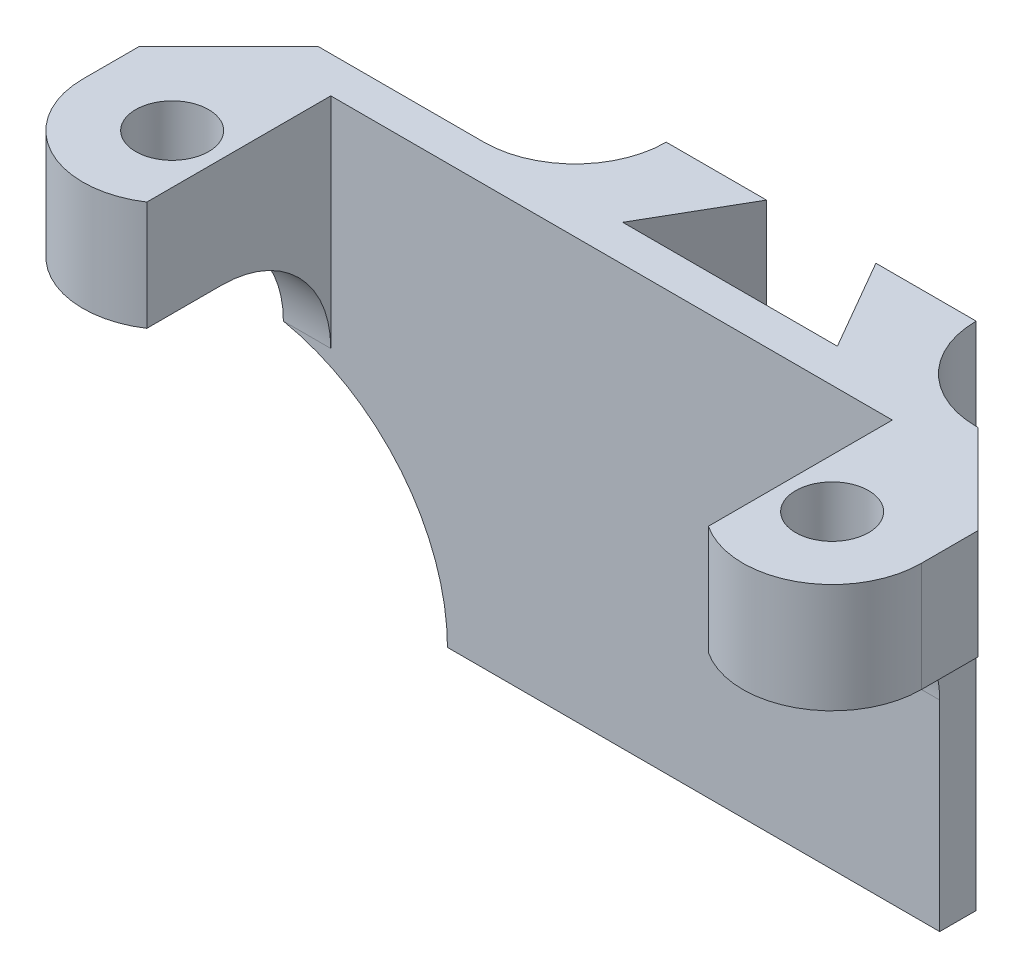
SolidWorks part; units mm, degrees
material "ABS"
ref_plane "Front Plane" through (0, 0, 0) normal (0, 0, 1) x (1, 0, 0)
ref_plane "Top Plane" through (0, 0, 0) normal (0, 1, 0) x (1, 0, 0)
ref_plane "Right Plane" through (0, 0, 0) normal (1, 0, 0) x (0, 0, -1)
sketch "Sketch1" plane through (0, 0, 0) normal (0, 0, 1) x (1, 0, 0)
  line L0 (-15, 15) -> (15, 15)
  line L1 (15, 15) -> (15, -15)
  line L2 (15, -15) -> (-15, -15)
  line L3 (-15, -15) -> (-15, 15)
  line L4 (-15, 0) -> (15, 0) construction
  line L5 (-15, 5) -> (-23, 5)
  line L6 (-23, 5) -> (-23, -1)
  line L7 (-23, -1) -> (-18, -1)
  line L8 (-18, -1) -> (-18, -18)
  line L9 (-18, -18) -> (18, -18)
  line L10 (18, -18) -> (18, -1)
  line L11 (18, -1) -> (23, -1)
  line L12 (23, -1) -> (23, 5)
  line L13 (23, 5) -> (15, 5)
  line L14 (-15, 5) -> (15, 5)
  point P6 (0, 0)
  dimension "D1" = 30
  dimension "D2" = 30
  dimension "D3" = 20
  dimension "D4" = 3
  dimension "D5" = 3
  dimension "D6" = 5
  dimension "D7" = 6
extrude "Extrude1" add sketch "Sketch1" along normal mid plane 16 contours L12 L13 L1 L2 L3 L5 L6 L7 L8 L9 L10 L11 | L4 L3 L2 L1 | L3 L4 L1 L14
sketch "Sketch2" plane through (0, 0, 0) normal (0, 1, 0) x (1, 0, 0)
  line L0 (-15.4, 0) -> (15.4, 0) construction
  line L1 (0, -6) -> (0, 6) construction
  line L2 (-15.4, -6) -> (-15.4, 6)
  line L3 (-15.4, 6) -> (15.4, 6)
  line L4 (15.4, 6) -> (15.4, -6)
  line L5 (15.4, -6) -> (-15.4, -6)
  line L6 (-18.1, 0) -> (-15.4, 0) construction
  line L7 (15.4, 0) -> (18.1, 0) construction
  line L8 (23, -3.1) -> (18.1, -8)
  line L9 (23, -8) -> (23, 8) construction
  line L11 (23, -8) -> (-23, -8) construction
  line L12 (18.1, -8) -> (23, -8)
  line L14 (23, -8) -> (23, -3.1)
  line L15 (18.1, 8) -> (23, 3.1)
  line L17 (23, 8) -> (-23, 8) construction
  line L18 (23, 3.1) -> (23, 8)
  line L20 (23, 8) -> (18.1, 8)
  line L21 (-18.1, 8) -> (-23, 3.1)
  line L22 (-23, -8) -> (-23, 8) construction
  line L23 (-23, 3.1) -> (-23, 8)
  line L24 (-23, 8) -> (-18.1, 8)
  line L25 (-23, -3.1) -> (-18.1, -8)
  line L26 (-18.1, -8) -> (-23, -8)
  line L27 (-23, -8) -> (-23, -3.1)
  line L28 (-11.4, 4) -> (11.4, 4)
  line L29 (-11.4, 4) -> (-11.4, -4)
  line L30 (-11.4, -4) -> (11.4, -4)
  line L31 (11.4, -4) -> (11.4, 4)
  circle A0 centre (-18.1, 0) radius 2
  circle A1 centre (18.1, 0) radius 2
  point P2 (0, 0)
  point P6 (0, 0)
  point P46 (-11.4, 0)
  point P47 (11.4, 0)
  dimension "D4" = 4
  dimension "D1" = 12
  dimension "D2" = 30.8
  dimension "D3" = 36.2
  dimension "D5" = 2
  dimension "D6" = 4
  dimension "D7" = 4
extrude "Extrude2" cut sketch "Sketch2" against normal blind 20 from surface at 5 contours L27 L26 L25 | A0 | L24 L23 L21 | L30 L31 L28 L29 | L5 L4 L3 L2 L31 L30 L29 L28 | L18 L20 L15 | A1 | L12 L14 L8 starting at face at (0, 5, 0)
sketch "Sketch5" plane through (0, 0, 0) normal (0, 0, 1) x (1, 0, 0)
  line L0 (-18, -1) -> (-18, -18)
  line L1 (18, -1) -> (18, -18)
  line L2 (18, -18) -> (-18, -18)
  line L3 (-18, -1) -> (18, -1)
extrude "Extrude10" cut sketch "Sketch5" along normal up to surface (14 mm away) from vertex
sketch "Sketch4" plane through (0, 0, 0) normal (0, 1, 0) x (1, 0, 0)
  line L0 (13, 8) -> (13, 13)
  line L1 (13, 13) -> (7.5, 13)
  line L2 (7.5, 13) -> (10.3868, 8)
  line L3 (18.1, 8) -> (-18.1, 8) construction
  line L4 (-4, 8) -> (-4, 13)
  line L5 (-4, 13) -> (1.5, 13)
  line L6 (1.5, 13) -> (-1.3868, 8)
  line L7 (-1.3868, 8) -> (-9, 8)
  line L8 (10.3868, 8) -> (18, 8)
  line L9 (18.1, 8) -> (-18.1, 8) construction
  line L10 (18.1, 8) -> (-18.1, 8) construction
  arc A0 (-4, 13) -> (-9, 8) centre (-9, 13) cw
  arc A1 (13, 13) -> (18, 8) centre (18, 13) ccw
  dimension "D1" = 5
  dimension "D2" = 17
  dimension "D3" = 6
  dimension "D4" = 60
extrude "Extrude6" add sketch "Sketch4" against normal up to surface (23 mm away) from vertex
sketch "Sketch6" plane through (0, 0, 0) normal (0, 1, 0) x (1, 0, 0)
  line L0 (-23, -3.1) -> (-23, 3.1) construction
  line L1 (-15.4, -6) -> (-15.4, 6) construction
  line L2 (23, -3.1) -> (23, 3.1) construction
  line L3 (15.4, 6) -> (15.4, -6) construction
  line L4 (-15.4, -4.089) -> (15.4, -4.089)
  line L5 (23, 0) -> (23, -8.8937)
  line L6 (23, -8.8937) -> (-23, -8.8937)
  line L7 (-23, -8.8937) -> (-23, 0)
  arc A0 (-23, 0) -> (-15.4, -4.089) centre (-18.1, 0) ccw
  circle A1 centre (-18.1, 0) radius 2 construction
  arc A2 (23, 0) -> (15.4, -4.089) centre (18.1, 0) cw
  circle A3 centre (18.1, 0) radius 2 construction
extrude "Extrude11" cut sketch "Sketch6" along normal up to vertex (5 mm away) from vertex at -1
fillet "Fillet1" radius 6 2 edges at (-16.7, -1, -6) (16.7, -1, -6)
fillet "Fillet2" radius 2 2 edges at (-18, -1, -4.9987) (18, -1, -4.9987)
sketch "Sketch8" plane through (0, 0, 0) normal (0, 0, 1) x (1, 0, 0)
  line L0 (-18, -7) -> (-18, -18)
  line L1 (-18, -18) -> (-9, -18)
  line L2 (-18, -18) -> (18, -18) construction
  line L4 (-9, 0) -> (-9, -18) construction
  line L5 (-18, -18) -> (18, -18) construction
  arc A0 (-18, -7) -> (-9, -18) centre (-20.2222, -18) cw
extrude "Extrude12" cut sketch "Sketch8" along normal up to surface (2 mm away) from surface at -8 up to face at (0, -6.75, -6) starting at face at (4.5, -6.5, -8)
